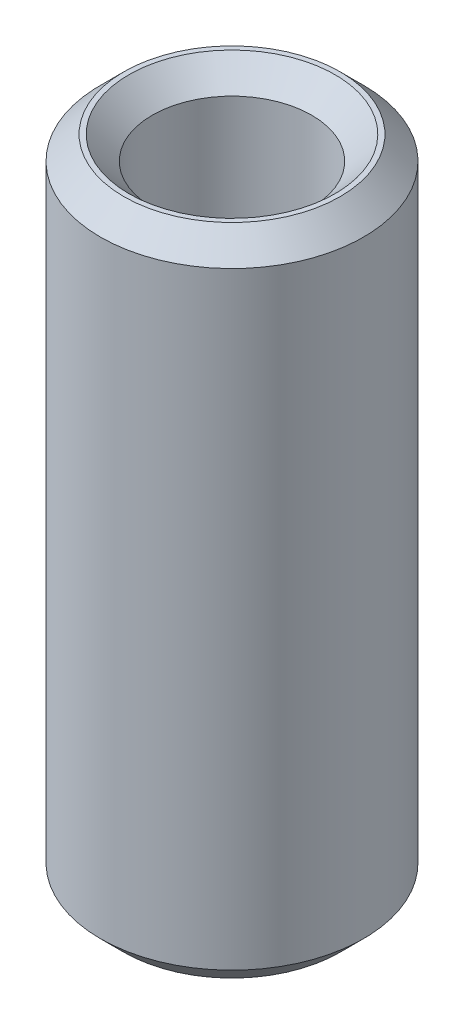
SolidWorks part; units mm, degrees
ref_plane "Front Plane" through (0, 0, 0) normal (0, 0, 1) x (1, 0, 0)
ref_plane "Top Plane" through (0, 0, 0) normal (0, 1, 0) x (1, 0, 0)
ref_plane "Right Plane" through (0, 0, 0) normal (1, 0, 0) x (0, 0, -1)
sketch "Sketch1" plane through (0, 0, 0) normal (0, 1, 0) x (1, 0, 0)
  circle A0 centre (0, 0) radius 10
  dimension "SLEEVE_OD" = 20
extrude "Boss-Extrude1" add sketch "Sketch1" along normal blind 49.7491
sketch "Sketch2" plane through (0, 0, 0) normal (0, 1, 0) x (1, 0, 0)
  circle A0 centre (0, 0) radius 6.0619
  dimension "BORE_D" = 12.1238
extrude "Cut-Extrude1" cut sketch "Sketch2" along normal through all
chamfer "Chamfer1" distance 1.7767 angle 45 4 edges at (0, 49.7491, 6.0619) (0, 0, 6.0619) (0, 0, 10) (0, 49.7491, 10)
